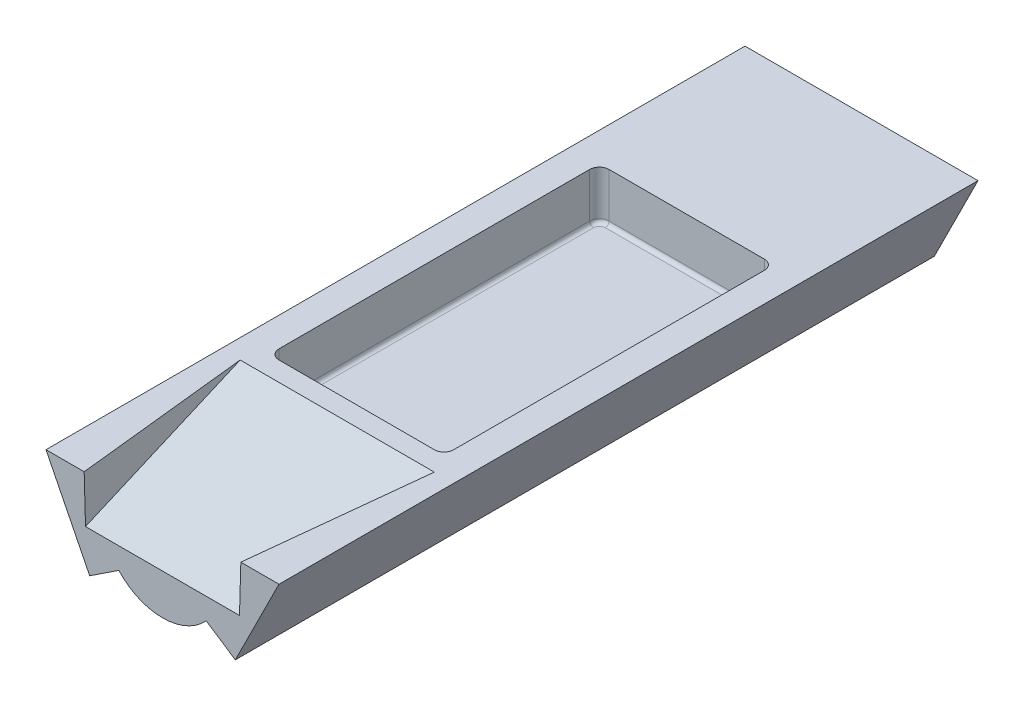
SolidWorks part; units mm, degrees
ref_plane "Front Plane" through (0, 0, 0) normal (0, 0, 1) x (1, 0, 0)
ref_plane "Top Plane" through (0, 0, 0) normal (0, 1, 0) x (1, 0, 0)
ref_plane "Right Plane" through (0, 0, 0) normal (1, 0, 0) x (0, 0, -1)
sketch "Sketch1" plane through (0, 0, 0) normal (0, 0, 1) x (1, 0, 0)
  line L6 (-304.8, 228.6) -> (304.8, 228.6)
  line L9 (0, 0) -> (0, 228.6) construction
  line L15 (-304.8, 228.6) -> (-190.5, 0)
  line L16 (-190.5, 0) -> (-114.3, 50.4)
  line L18 (190.5, 0) -> (304.8, 228.6)
  line L19 (190.5, 0) -> (114.3, 50.4)
  arc A0 (-114.3, 50.4) -> (114.3, 50.4) centre (0, 154.808) ccw
  dimension "D1" = 609.6
  dimension "D2" = 228.6
  dimension "D3" = 228.6
  dimension "D4" = 114.3
  dimension "D5" = 114.3
  dimension "D6" = 76.2
  dimension "D7" = 76.2
extrude "Boss-Extrude2" add sketch "Sketch1" against normal blind 1828.8
sketch "Sketch2" plane through (0, 228.6, 0) normal (0, 1, 0) x (1, 0, 0)
  line L1 (-203.2, 0) -> (203.2, 0)
  line L3 (-254, 457.2) -> (254, 457.2)
  line L6 (-254, 457.2) -> (-203.2, 0)
  line L7 (254, 457.2) -> (203.2, 0)
  line L8 (304.8, 0) -> (-304.8, 0) construction
  dimension "D1" = 508
  dimension "D2" = 457.2
  dimension "D3" = 50.8
  dimension "D4" = 50.8
ref_plane "Plane1" through (0, 98.9867, 26.5234) normal (0, 0.9659, 0.2588) x (1, 0, 0)
sketch "Sketch7" plane through (0, 98.9867, 26.5234) normal (0, 0.9659, 0.2588) x (1, 0, 0)
  line L1 (-254, 500.7873) -> (254, 500.7873)
  line L2 (-254, 500.7873) -> (-196.5534, -16.2318)
  line L3 (254, 500.7873) -> (196.5534, -16.2318)
  line L6 (-196.5534, -16.2318) -> (196.5534, -16.2318)
  dimension "D1" = 508
extrude "Cut-Extrude2" cut sketch "Sketch7" along normal through all
sketch "Sketch8" plane through (0, 228.6, 0) normal (0, 1, 0) x (1, 0, 0)
  line L0 (-304.8, 1828.8) -> (-304.8, 0) construction
  line L1 (-228.6, 508) -> (228.6, 508)
  line L2 (-228.6, 508) -> (-228.6, 1371.6)
  line L3 (-228.6, 1371.6) -> (228.6, 1371.6)
  line L4 (228.6, 508) -> (228.6, 1371.6)
  line L5 (254, 457.2) -> (-254, 457.2) construction
  dimension "D1" = 457.2
  dimension "D2" = 863.6
  dimension "D3" = 76.2
  dimension "D4" = 50.8
extrude "Cut-Extrude5" cut sketch "Sketch8" against normal blind 127
fillet "Fillet1" radius 10 4 edges at (0, 101.6, -1371.6) (228.6, 101.6, -939.8) (0, 101.6, -508) (-228.6, 101.6, -939.8)
fillet "Fillet2" radius 25.4 8 edges at (225.6711, 104.5289, -510.9289) (-225.6711, 104.5289, -510.9289) (-228.6, 170.1, -508) (228.6, 170.1, -508) (-225.6711, 104.5289, -1368.6711) (225.6711, 104.5289, -1368.6711) (228.6, 170.1, -1371.6) (-228.6, 170.1, -1371.6)
